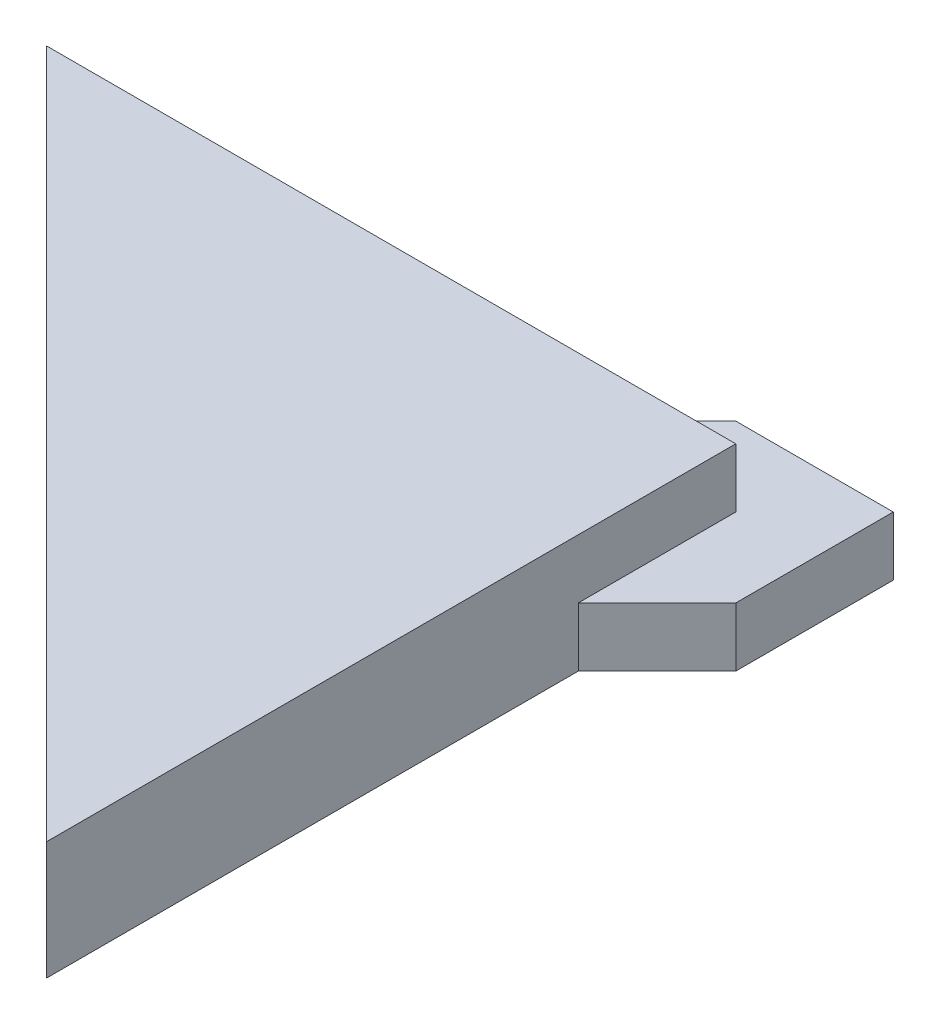
SolidWorks part; units mm, degrees
ref_plane "Front Plane" through (0, 0, 0) normal (0, 0, 1) x (1, 0, 0)
ref_plane "Top Plane" through (0, 0, 0) normal (0, 1, 0) x (1, 0, 0)
ref_plane "Right Plane" through (0, 0, 0) normal (1, 0, 0) x (0, 0, -1)
sketch "Sketch1" plane through (0, 0, 0) normal (0, 1, 0) x (1, 0, 0)
  line L0 (0, 0) -> (0, 35)
  line L1 (0, 35) -> (-35, 35)
  line L2 (-35, 35) -> (0, 0)
  line L3 (-8, 35) -> (-4, 39)
  line L4 (-4, 39) -> (4, 39)
  line L5 (4, 39) -> (4, 31)
  line L6 (4, 31) -> (0, 27)
  dimension "D1" = 35
  dimension "D2" = 8
  dimension "D3" = 4
  dimension "D4" = 35
extrude "Boss-Extrude1" add sketch "Sketch1" along normal blind 6 contours L1 L2 L0 region at (-11.6667, 0, -23.3333)
extrude "Boss-Extrude2" add sketch "Sketch1<3>" along normal blind 3 contours L6 L5 L4 L3 L1 L0 region at (0.1697, 0, -31)
sketch "Sketch1<3>" plane through (0, 0, 0) normal (0, 1, 0) x (1, 0, 0) same geometry as "Sketch1"
